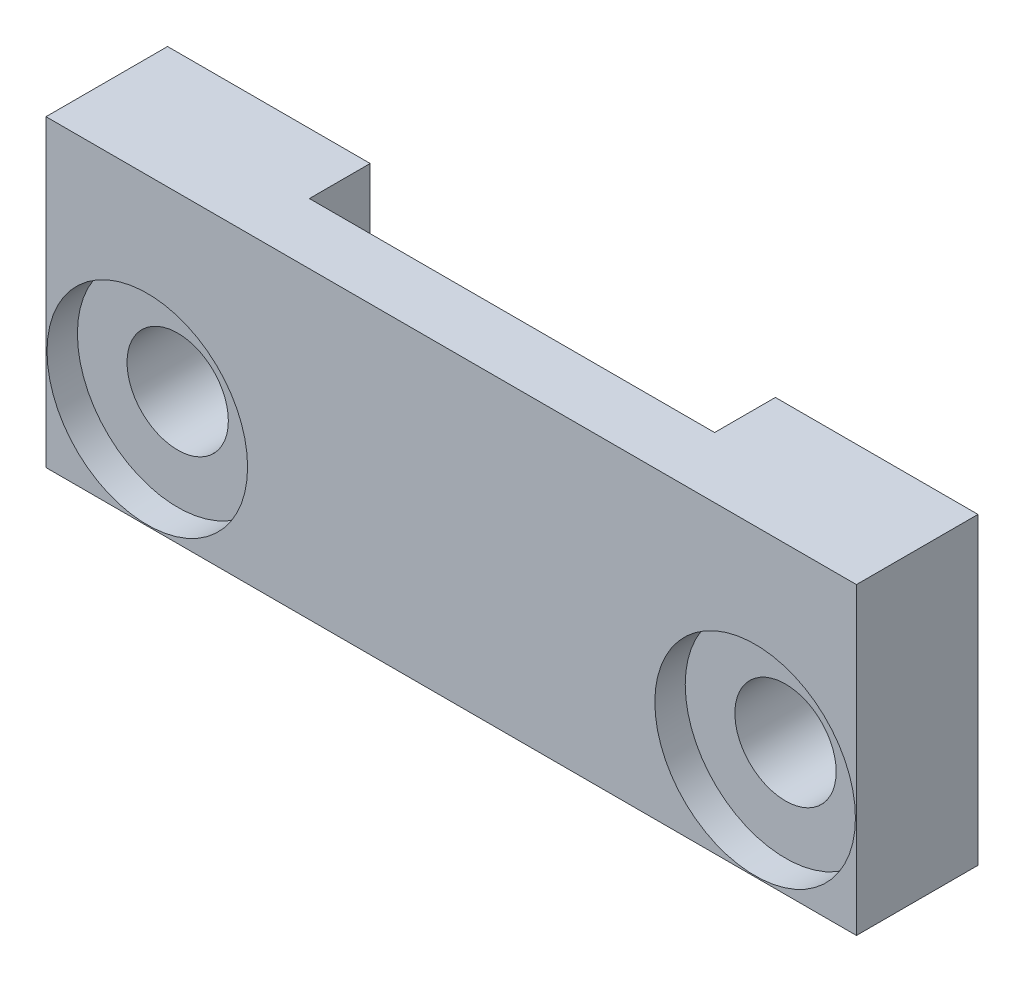
SolidWorks part; units mm, degrees
ref_plane "Front" through (0, 0, 0) normal (0, 0, 1) x (1, 0, 0)
ref_plane "Top" through (0, 0, 0) normal (0, 1, 0) x (1, 0, 0)
ref_plane "Right" through (0, 0, 0) normal (1, 0, 0) x (0, 0, -1)
other "Configuration Table"
sketch "Sketch1" plane through (0, 0, 0) normal (0, 0, 1) x (1, 0, 0)
  line L0 (-22.5328, 19.4359) -> (-22.5328, 4.4359) construction
  line L1 (-42.5328, 19.4359) -> (-2.5328, 19.4359)
  line L2 (-42.5328, 19.4359) -> (-42.5328, 4.4359)
  line L3 (-42.5328, 4.4359) -> (-2.5328, 4.4359)
  line L4 (-2.5328, 19.4359) -> (-2.5328, 4.4359)
  line L5 (-32.5328, 4.4359) -> (-32.5328, 19.4359)
  line L6 (-12.5328, 4.4359) -> (-12.5328, 19.4359)
  circle A0 centre (-37.5328, 9.4359) radius 2.5
  circle A1 centre (-37.5328, 9.4359) radius 4.95
  circle A2 centre (-7.5328, 9.4359) radius 2.5
  circle A3 centre (-7.5328, 9.4359) radius 4.95
  dimension "D3" = 5
  dimension "D4" = 9.9
  dimension "D1" = 15
  dimension "D2" = 40
  dimension "D5" = 5
  dimension "D6" = 5
  dimension "D7" = 10
extrude "Boss-Extrude1" add sketch "Sketch1" along normal blind 3 contours A1 A0 | L3 L5 L1 L2 A1 | A3 A2 | L6 L3 L4 L1 A3 | L1 L0 L3 L6 | L0 L1 L5 L3 region at (-17.5328, 11.9359, 0) region at (-27.5328, 11.9359, 0) region at (-37.5328, 14.5713, 0) region at (-7.5328, 14.5713, 0) region at (-42.3428, 9.4359, 0) region at (-12.3428, 9.4359, 0)
extrude "Boss-Extrude2" add sketch "Sketch1<3>" against normal blind 3 contours L3 L5 L1 L2 A1 | A1 A0 | A3 A2 | L6 L3 L4 L1 A3 region at (-37.5328, 14.5713, 0) region at (-7.5328, 14.5713, 0) region at (-42.3428, 9.4359, 0) region at (-12.3428, 9.4359, 0)
sketch "Sketch1<3>" plane through (0, 0, 0) normal (0, 0, 1) x (1, 0, 0) same geometry as "Sketch1"
extrude "Cut-Extrude1" cut sketch "Sketch1<4>" against normal blind 1.5 from surface contours A1 A0 | A3 A2 region at (-42.3428, 9.4359, 0) region at (-12.3428, 9.4359, 0) starting at face at (-35.0328, 9.4359, 3)
sketch "Sketch1<4>" plane through (0, 0, 0) normal (0, 0, 1) x (1, 0, 0) same geometry as "Sketch1"
